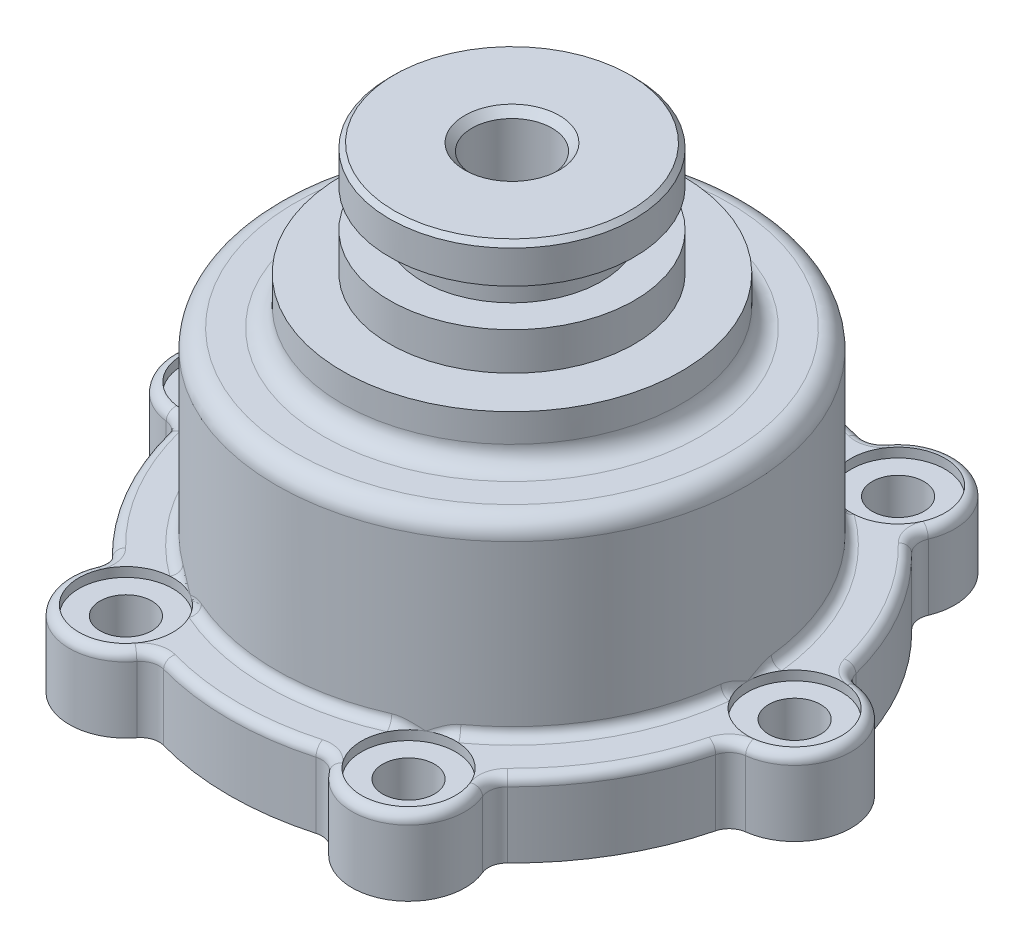
SolidWorks part; units mm, degrees
ref_plane "前视基准面" through (0, 0, 0) normal (0, 0, 1) x (1, 0, 0)
ref_plane "上视基准面" through (0, 0, 0) normal (0, 1, 0) x (1, 0, 0)
ref_plane "右视基准面" through (0, 0, 0) normal (1, 0, 0) x (0, 0, -1)
other "Configuration Table"
sketch "草图1" plane through (0, 0, 0) normal (1, 0, 0) x (0, 0, -1)
  line L0 (0, 0) -> (13, 0)
  line L1 (13, 0) -> (13, -4)
  line L2 (13, -4) -> (9.5, -4)
  line L3 (9.5, -4) -> (9.5, -8)
  line L4 (9.5, -8) -> (13, -8)
  line L5 (13, -8) -> (13, -12)
  line L6 (13, -12) -> (18, -12)
  line L7 (18, -12) -> (18, -17)
  line L8 (18, -17) -> (25, -17)
  line L9 (25, -17) -> (25, -37)
  line L10 (25, -37) -> (30, -37)
  line L11 (30, -37) -> (30, -45)
  line L12 (30, -45) -> (20, -45)
  line L13 (20, -45) -> (20, -21)
  line L14 (20, -21) -> (0, -21)
  line L15 (0, -21) -> (0, 0)
  dimension "D1" = 13
  dimension "D2" = 4
  dimension "D3" = 9.5
  dimension "D4" = 4
  dimension "D5" = 12
  dimension "D6" = 90
  dimension "D7" = 18
  dimension "D8" = 13
  dimension "D9" = 45
  dimension "D10" = 20
  dimension "D11" = 20
  dimension "D12" = 30
  dimension "D13" = 24
  dimension "D14" = 8
  dimension "D15" = 21
  dimension "D16" = 25
revolve "旋转1" add sketch "草图1" angle 360 about L15
hole_wizard "M10 螺纹孔1" positions "草图2" profile "草图3" tap size "M10" standard "GB" end condition through all
sketch "草图2" plane through (0, 0, 0) normal (0, 1, 0) x (1, 0, 0)
  point P0 (0, 0)
sketch "草图3" plane through (0, 0, 0) normal (1, 0, 0) x (0, 0, 1)
  line L0 (0, 0) -> (0, 45)
  line L1 (0, 45) -> (4.25, 45)
  line L2 (4.25, 45) -> (4.25, 0.775)
  line L3 (4.25, 0.775) -> (5.025, 0)
  line L5 (5.025, 0) -> (0, 0)
  line L6 (-4.25, 0.775) -> (-5.025, 0) construction
  line L11 (0, -6.35) -> (0, 107.95) construction
  dimension "通孔螺纹孔钻头直径" = 8.5
  dimension "通孔螺纹孔钻头深度" = 45
  dimension "近端锥形沉头孔直径" = 10.05
  dimension "近端锥形沉头孔角度" = 90
cosmetic thread "孔螺蚊线1" parameters "D2"=10
chamfer "倒角1" distance 0.5 angle 45 1 edges at (0, 0, -13)
fillet "圆角1" radius 2 3 edges at (0, -21, -20) (0, -17, -18) (0, -17, -25)
sketch "草图4" plane through (0, -45, 0) normal (0, -1, 0) x (1, 0, 0)
  line L1 (0, 0) -> (15, 25.9808) construction
  arc A0 (19.8701, 22.4762) -> (9.5299, 28.4461) centre (15, 25.9808) ccw
  circle A1 centre (0, 0) radius 30 construction
  arc A2 (-19.8701, 22.4762) -> (-29.4, 5.9699) centre (0, 0) ccw
  arc A3 (29.4, -5.9699) -> (29.4, 5.9699) centre (30, 0) ccw
  arc A4 (9.5299, -28.4461) -> (19.8701, -22.4762) centre (15, -25.9808) ccw
  arc A5 (-19.8701, -22.4762) -> (-9.5299, -28.4461) centre (-15, -25.9808) ccw
  arc A6 (-29.4, 5.9699) -> (-29.4, -5.9699) centre (-30, 0) ccw
  arc A7 (-9.5299, 28.4461) -> (-19.8701, 22.4762) centre (-15, 25.9808) ccw
  arc A8 (-29.4, -5.9699) -> (-19.8701, -22.4762) centre (0, 0) ccw
  arc A9 (9.5299, 28.4461) -> (-9.5299, 28.4461) centre (0, 0) ccw
  arc A10 (29.4, 5.9699) -> (19.8701, 22.4762) centre (0, 0) ccw
  arc A11 (19.8701, -22.4762) -> (29.4, -5.9699) centre (0, 0) ccw
  arc A12 (-9.5299, -28.4461) -> (9.5299, -28.4461) centre (0, 0) ccw
  circle A13 centre (0, 0) radius 20
  point P21 (0, 0)
  dimension "D2" = 12
  dimension "D3" = 6
extrude "凸台-拉伸2" add sketch "草图4" against normal blind 8 contours A7 A2 A6 A8 A5 A12 A4 A11 A3 A10 A0 A9 | A13
fillet "圆角3" radius 2 12 edges at (-9.5299, -41, -28.4461) (9.5299, -41, -28.4461) (19.8701, -41, -22.4762) (29.4, -41, -5.9699) (29.4, -41, 5.9699) (19.8701, -41, 22.4762) (9.5299, -41, 28.4461) (-9.5299, -41, 28.4461) (-19.8701, -41, 22.4762) (-29.4, -41, 5.9699) (-29.4, -41, -5.9699) (-19.8701, -41, -22.4762)
sketch "草图7" plane through (0, -37, 0) normal (0, 1, 0) x (1, 0, 0)
  circle A0 centre (-15, 25.9808) radius 2.75
  circle A1 centre (15, 25.9808) radius 2.75
  circle A2 centre (30, 0) radius 2.75
  circle A3 centre (15, -25.9808) radius 2.75
  circle A4 centre (-15, -25.9808) radius 2.75
  circle A5 centre (-30, 0) radius 2.75
  point P15 (0, 0)
  dimension "D1" = 5.5
  dimension "D2" = 6
extrude "切除-拉伸1" cut sketch "草图7" against normal through all
sketch "草图8" plane through (0, -37, 0) normal (0, 1, 0) x (1, 0, 0)
  circle A0 centre (-15, 25.9808) radius 5
  circle A1 centre (15, 25.9808) radius 5
  circle A2 centre (30, 0) radius 5
  circle A3 centre (15, -25.9808) radius 5
  circle A4 centre (-15, -25.9808) radius 5
  circle A5 centre (-30, 0) radius 5
  point P15 (0, 0)
  dimension "D1" = 10
  dimension "D2" = 6
extrude "切除-拉伸2" cut sketch "草图8" against normal blind 1 and the other way blind 1 contours A5 | A0 | A1 | A2 | A3 | A4
fillet "圆角4" radius 1 24 edges at (9.2637, -37, -28.9198) (0, -37, -30) (-9.2637, -37, -28.9198) (-18, -37, -31.1769) (-20.4134, -37, -22.4825) (-25.9808, -37, -15) (-29.6771, -37, -6.4373) (-36, -37, 0) (-29.6771, -37, 6.4373) (-25.9808, -37, 15) (-20.4134, -37, 22.4825) (-18, -37, 31.1769) (-9.2637, -37, 28.9198) (0, -37, 30) (9.2637, -37, 28.9198) (18, -37, 31.1769) (20.4134, -37, 22.4825) (25.9808, -37, 15) (29.6771, -37, 6.4373) (36, -37, 0) (29.6771, -37, -6.4373) (25.9808, -37, -15) (20.4134, -37, -22.4825) (18, -37, -31.1769)
fillet "圆角5" radius 1 6 edges at (21.6506, -37, 12.5) (21.6506, -37, -12.5) (0, -37, -25) (-21.6506, -37, -12.5) (-21.6506, -37, 12.5) (0, -37, 25)
